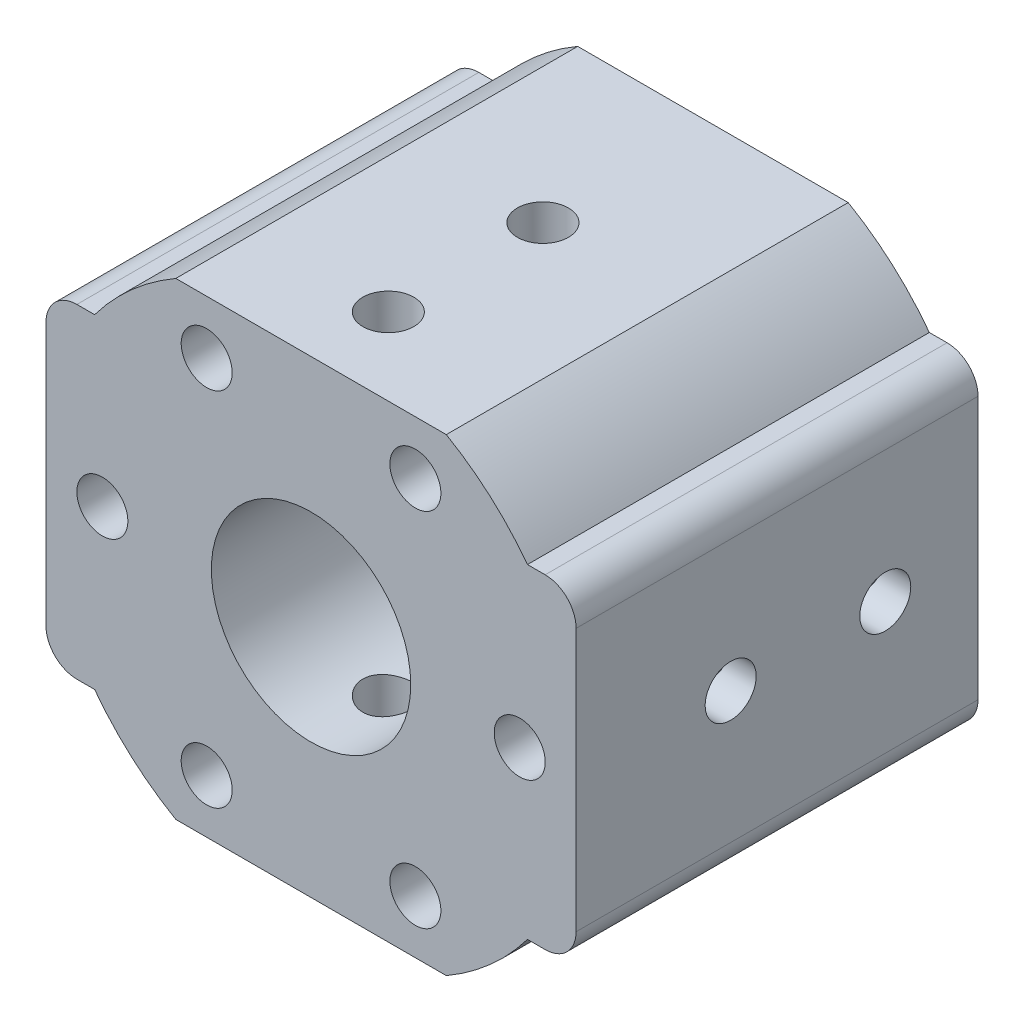
SolidWorks part; units mm, degrees
material "PLA"
ref_plane "前视基准面" through (0, 0, 0) normal (0, 0, 1) x (1, 0, 0)
ref_plane "上视基准面" through (0, 0, 0) normal (0, 1, 0) x (1, 0, 0)
ref_plane "右视基准面" through (0, 0, 0) normal (1, 0, 0) x (0, 0, -1)
other "Configuration Table"
sketch "草图1" plane through (0, 0, 0) normal (0, 0, 1) x (1, 0, 0)
  line L1 (17.5, 0) -> (8.75, 15.1554)
  line L2 (8.75, 15.1554) -> (-8.75, 15.1554)
  line L3 (-8.75, 15.1554) -> (-17.5, 0)
  line L4 (-17.5, 0) -> (-8.75, -15.1554)
  line L5 (-8.75, -15.1554) -> (8.75, -15.1554)
  line L6 (8.75, -15.1554) -> (17.5, 0)
  circle A1 centre (13.5, 0) radius 1.65 construction
  circle A2 centre (6.75, -11.6913) radius 1.65 construction
  circle A3 centre (-6.75, -11.6913) radius 1.65 construction
  circle A4 centre (-13.5, 0) radius 1.65 construction
  circle A5 centre (-6.75, 11.6913) radius 1.65 construction
  circle A6 centre (6.75, 11.6913) radius 1.65 construction
  arc A7 (-8.75, 15.1554) -> (-8.75, -15.1554) centre (0, 0) ccw
  arc A8 (8.75, -15.1554) -> (8.75, 15.1554) centre (0, 0) ccw
  point P17 (0, 0)
  dimension "D1" = 13.5
  dimension "D2" = 35
  dimension "D3" = 3.3
  dimension "D4" = 6
extrude "凸台-拉伸1" add sketch "草图1" along normal blind 30 contours L5 L6 L1 L2 L3 L4 A6 A5 A4 A3 A2 A1 | L3 A7 | L4 A7 | L1 A8 | L6 A8 region at (0, 0, 0) region at (13.942, -8.0494, 0) region at (13.942, 8.0494, 0) region at (-13.942, 8.0494, 0) region at (-13.942, -8.0494, 0)
sketch "草图3" plane through (0, 0, 30) normal (0, 0, 1) x (1, 0, 0)
  line L1 (-4.45, 4.45) -> (4.45, 4.45) construction
  line L2 (-4.45, 4.45) -> (-4.45, -4.45) construction
  line L3 (-4.45, -4.45) -> (4.45, -4.45) construction
  line L4 (4.45, 4.45) -> (4.45, -4.45) construction
  line L5 (-4.45, 4.45) -> (4.45, -4.45) construction
  line L6 (-4.45, -4.45) -> (4.45, 4.45) construction
  circle A0 centre (0, 0) radius 6.45
  point P0 (0, 0)
  dimension "D3" = 12.9
  dimension "D1" = 8.9
  dimension "D2" = 8.9
extrude "切除-拉伸1" cut sketch "草图3" against normal through all
sketch "草图4" plane through (0, 15.1554, 0) normal (0, 1, 0) x (1, 0, 0)
  line L0 (8.75, -30) -> (-8.75, -30) construction
  circle A0 centre (0, -15) radius 1.65
  circle A1 centre (0, -25) radius 1.65
  dimension "D1" = 5
  dimension "D2" = 10
  dimension "D3" = 3.3
extrude "切除-拉伸2" cut sketch "草图4" against normal through all
sketch "草图6" [suppressed] plane through (0, 0, 30) normal (0, 0, 1) x (1, 0, 0)
  circle A0 centre (-6.75, 11.6913) radius 3.25
  circle A1 centre (6.75, 11.6913) radius 3.25
  circle A2 centre (13.5, 0) radius 3.25
  circle A3 centre (6.75, -11.6913) radius 3.25
  circle A4 centre (-6.75, -11.6913) radius 3.25
  circle A5 centre (-13.5, 0) radius 3.25
  point P16 (0, 0)
  dimension "D1" = 6.5
  dimension "D2" = 6
extrude "切除-拉伸3" [suppressed] cut sketch "草图6" against normal blind 5
sketch "草图7" plane through (0, 0, 0) normal (1, 0, 0) x (0, 0, -1)
  line L0 (0, 0) -> (-25.3477, 0) construction
  line L1 (-30, 15.1554) -> (-30, -15.1554) construction
  line L2 (-30, 3.5) -> (0, 3.5)
  line L3 (-30, 3.5) -> (-30, 10.5)
  line L4 (-30, 10.5) -> (0, 10.5)
  line L5 (0, 3.5) -> (0, 10.5)
  line L6 (0, -15.1554) -> (0, 15.1554) construction
  line L7 (0, -3.5) -> (0, -10.5)
  line L8 (-30, -3.5) -> (0, -3.5)
  line L9 (-30, -3.5) -> (-30, -10.5)
  line L10 (-30, -10.5) -> (0, -10.5)
  dimension "D1" = 7
  dimension "D2" = 3.5
extrude "切除-拉伸4" cut sketch "草图7" against normal blind 30 from offset 14 offset against normal yes
extrude "切除-拉伸5" cut sketch "草图7<2>" along normal blind 30 from offset 14
sketch "草图7<2>" plane through (0, 0, 0) normal (1, 0, 0) x (0, 0, -1) same geometry as "草图7"
sketch "草图10" plane through (-14, 0, 0) normal (-1, 0, 0) x (0, 0, 1)
  line L0 (30, -3.5) -> (0, -3.5) construction
  line L1 (0, -3.5) -> (0, -10.5) construction
  line L2 (0, -10.5) -> (30, -10.5) construction
  line L3 (30, -10.5) -> (30, -3.5) construction
  line L4 (30, 3.5) -> (30, 10.5) construction
  line L5 (30, 10.5) -> (0, 10.5) construction
  line L6 (0, 10.5) -> (0, 3.5) construction
  line L7 (0, 3.5) -> (30, 3.5) construction
  line L8 (30, -3.5) -> (0, -3.5)
  line L9 (0, -3.5) -> (0, -10.5)
  line L10 (0, -10.5) -> (30, -10.5)
  line L11 (30, -10.5) -> (30, -3.5)
  line L12 (30, 3.5) -> (30, 10.5)
  line L13 (30, 10.5) -> (0, 10.5)
  line L14 (0, 10.5) -> (0, 3.5)
  line L15 (0, 3.5) -> (30, 3.5)
extrude "凸台-拉伸2" add sketch "草图10" along normal up to vertex (3.1464 mm away) up to point (-17.1464, 3.5, 30)
sketch "草图11" plane through (14, 0, 0) normal (1, 0, 0) x (0, 0, -1)
  line L0 (0, -3.5) -> (-30, -3.5) construction
  line L1 (-30, -3.5) -> (-30, -10.5) construction
  line L2 (-30, -10.5) -> (0, -10.5) construction
  line L3 (0, -10.5) -> (0, -3.5) construction
  line L4 (-30, 10.5) -> (-30, 3.5) construction
  line L5 (-30, 3.5) -> (0, 3.5) construction
  line L6 (0, 3.5) -> (0, 10.5) construction
  line L7 (0, 10.5) -> (-30, 10.5) construction
  line L8 (0, -3.5) -> (-30, -3.5)
  line L9 (-30, -3.5) -> (-30, -10.5)
  line L10 (-30, -10.5) -> (0, -10.5)
  line L11 (0, -10.5) -> (0, -3.5)
  line L12 (-30, 10.5) -> (-30, 3.5)
  line L13 (-30, 3.5) -> (0, 3.5)
  line L14 (0, 3.5) -> (0, 10.5)
  line L15 (0, 10.5) -> (-30, 10.5)
extrude "凸台-拉伸3" add sketch "草图11" along normal up to vertex (3.1464 mm away) up to point (17.1464, 3.5, 30)
sketch "草图12" plane through (-17.1464, 0, 0) normal (-1, 0, 0) x (0, 0, 1)
  line L0 (20, 15.1554) -> (20, -15.1554) construction
  line L1 (16.65, 15.1554) -> (13.35, 15.1554) construction
  line L2 (26.65, 15.1554) -> (23.35, 15.1554) construction
  line L3 (16.65, 15.1554) -> (13.35, 15.1554) construction
  line L4 (26.65, 15.1554) -> (23.35, 15.1554) construction
  line L7 (16.65, 15.1554) -> (23.35, 15.1554) construction
  circle A2 centre (20, 0) radius 1.65
  dimension "D1" = 3.3
extrude "切除-拉伸6" cut sketch "草图12" against normal through all
sketch "草图14" plane through (0, -15.1554, 0) normal (0, -1, 0) x (1, 0, 0)
  line L1 (-17.1464, 30) -> (-20.1283, 30)
  line L2 (-17.1464, 30) -> (-17.1464, -0.8267)
  line L3 (-17.1464, -0.8267) -> (-20.1283, -0.8267)
  line L4 (-20.1283, 30) -> (-20.1283, -0.8267)
  line L5 (17.1464, 30) -> (20.3756, 30)
  line L6 (17.1464, 30) -> (17.1464, -1.7911)
  line L7 (17.1464, -1.7911) -> (20.3756, -1.7911)
  line L8 (20.3756, 30) -> (20.3756, -1.7911)
extrude "切除-拉伸7" cut sketch "草图14" against normal through all
sketch "草图16" [suppressed] plane through (0, 0, 10) normal (0, 0, 1) x (1, 0, 0)
  circle A0 centre (0, 0) radius 6.8
  dimension "D1" = 13.6
extrude "切除-拉伸8" [suppressed] cut sketch "草图16" against normal through all
sketch "草图17" plane through (17.1464, 0, 0) normal (1, 0, 0) x (0, 0, -1)
  circle A0 centre (-10, 0) radius 1.65
  circle A1 centre (-20, 0) radius 1.65 construction
  dimension "D1" = 10
extrude "切除-拉伸9" cut sketch "草图17" against normal through all
sketch "草图18" plane through (0, 0, 0) normal (0, 0, -1) x (-1, 0, 0)
  line L6 (-14, 10.5) -> (-17.1464, 10.5)
  line L8 (17.1464, -10.5) -> (17.1464, 10.5)
  line L9 (17.1464, 10.5) -> (14, 10.5)
  line L10 (8.75, 15.1554) -> (-8.75, 15.1554)
  line L13 (-14, 10.5) -> (-17.1464, 10.5)
  line L14 (-8.75, -15.1554) -> (8.75, -15.1554)
  line L15 (14, -10.5) -> (17.1464, -10.5)
  line L16 (17.1464, -10.5) -> (17.1464, 10.5)
  line L17 (17.1464, 10.5) -> (14, 10.5)
  line L18 (8.75, 15.1554) -> (-8.75, 15.1554)
  line L22 (-8.75, -15.1554) -> (8.75, -15.1554)
  line L23 (14, -10.5) -> (17.1464, -10.5)
  line L24 (-17.1464, 10.5) -> (-17.1464, -10.5)
  line L25 (-17.1464, 10.5) -> (-17.1464, -10.5)
  line L26 (-17.1464, -10.5) -> (-14, -10.5)
  line L27 (-17.1464, -10.5) -> (-14, -10.5)
  arc A4 (14, 10.5) -> (8.75, 15.1554) centre (0, 0) ccw
  arc A5 (-8.75, 15.1554) -> (-14, 10.5) centre (0, 0) ccw
  arc A6 (-14, -10.5) -> (-8.75, -15.1554) centre (0, 0) ccw
  arc A7 (8.75, -15.1554) -> (14, -10.5) centre (0, 0) ccw
  arc A8 (14, 10.5) -> (8.75, 15.1554) centre (0, 0) ccw
  arc A9 (-8.75, 15.1554) -> (-14, 10.5) centre (0, 0) ccw
  arc A11 (8.75, -15.1554) -> (14, -10.5) centre (0, 0) ccw
  arc A13 (-14, -10.5) -> (-8.75, -15.1554) centre (0, 0) ccw
  dimension "D1" = 0
extrude "切除-拉伸10" cut sketch "草图18" against normal blind 5
sketch "草图19" plane through (0, 0, 30) normal (0, 0, 1) x (1, 0, 0)
  circle A0 centre (13.5, 0) radius 1.65
  circle A1 centre (6.75, -11.6913) radius 1.65
  circle A2 centre (-6.75, -11.6913) radius 1.65
  circle A3 centre (-13.5, 0) radius 1.65
  circle A4 centre (-6.75, 11.6913) radius 1.65
  circle A5 centre (6.75, 11.6913) radius 1.65
  point P16 (0, 0)
  dimension "D1" = 13.5
  dimension "D2" = 3.3
  dimension "D3" = 6
extrude "切除-拉伸11" cut sketch "草图19" against normal through all
fillet "圆角1" radius 2 4 edges at (17.1464, -10.5, 17.5) (17.1464, 10.5, 17.5) (-17.1464, -10.5, 17.5) (-17.1464, 10.5, 17.5)
ref_plane "基准面1" [suppressed] through (0, 0, 9) normal (0, 0, 1) x (1, 0, 0)
mirror "镜向2" [suppressed] about plane through (0, 0, 9) normal (0, 0, 1) of bodies 115
sketch "草图21" [suppressed] plane through (0, 15.1554, 0) normal (0, 1, 0) x (1, 0, 0)
  line L0 (17.1464, -9) -> (-40.6903, -9) construction
  line L1 (17.1464, 12) -> (17.1464, -30) construction
  circle A0 centre (0, -3) radius 1.65
  circle A1 centre (0, -15) radius 1.65
  circle A2 centre (0, -25) radius 1.65 construction
  dimension "D1" = 10
extrude "切除-拉伸12" [suppressed] cut sketch "草图21" against normal through all
sketch "草图22" [suppressed] plane through (0, 0, 18) normal (0, 0, 1) x (1, 0, 0)
  line L4 (-7.85, -7.85) -> (7.85, -7.85)
  line L5 (7.85, -7.85) -> (7.85, 7.85)
  line L6 (7.85, 7.85) -> (-7.85, 7.85)
  line L7 (-7.85, 7.85) -> (-7.85, -7.85)
  line L8 (-7.85, -7.85) -> (7.85, -7.85)
  line L9 (7.85, -7.85) -> (7.85, 7.85)
  line L10 (7.85, 7.85) -> (-7.85, 7.85)
  line L11 (-7.85, 7.85) -> (-7.85, -7.85)
  dimension "D1" = 0
extrude "切除-拉伸13" [suppressed] cut sketch "草图22" against normal through all
sketch "草图23" [suppressed] plane through (0, 0, -12) normal (0, 0, -1) x (-1, 0, 0)
  line L0 (7.85, -7.85) -> (-7.85, -7.85) construction
  line L1 (-6.35, 6.35) -> (6.35, 6.35)
  line L2 (-6.35, 6.35) -> (-6.35, -6.35)
  line L3 (-6.35, -6.35) -> (6.35, -6.35)
  line L4 (6.35, 6.35) -> (6.35, -6.35)
  line L5 (-6.35, 6.35) -> (6.35, -6.35) construction
  line L6 (-6.35, -6.35) -> (6.35, 6.35) construction
  line L7 (7.85, 7.85) -> (7.85, -7.85) construction
  line L8 (-7.85, 7.85) -> (7.85, 7.85) construction
  line L9 (-7.85, -7.85) -> (-7.85, 7.85) construction
  line L10 (7.85, -7.85) -> (-7.85, -7.85)
  line L11 (7.85, 7.85) -> (7.85, -7.85)
  line L12 (-7.85, 7.85) -> (7.85, 7.85)
  line L13 (-7.85, -7.85) -> (-7.85, 7.85)
  point P0 (0, 0)
  dimension "D1" = 12.7
  dimension "D2" = 12.7
extrude "凸台-拉伸5" [suppressed] add sketch "草图23" against normal blind 21
sketch "草图24" plane through (0, 0, 5) normal (0, 0, -1) x (-1, 0, 0)
  line L8 (-17.1464, 8.5) -> (-17.1464, -8.5)
  line L9 (-15.1464, -10.5) -> (-14, -10.5)
  line L10 (-8.75, -15.1554) -> (8.75, -15.1554)
  line L11 (14, -10.5) -> (15.1464, -10.5)
  line L12 (17.1464, -8.5) -> (17.1464, 8.5)
  line L13 (15.1464, 10.5) -> (14, 10.5)
  line L14 (8.75, 15.1554) -> (-8.75, 15.1554)
  line L15 (-14, 10.5) -> (-15.1464, 10.5)
  line L16 (-17.1464, 8.5) -> (-17.1464, -8.5)
  line L17 (-15.1464, -10.5) -> (-14, -10.5)
  line L18 (-8.75, -15.1554) -> (8.75, -15.1554)
  line L19 (14, -10.5) -> (15.1464, -10.5)
  line L20 (17.1464, -8.5) -> (17.1464, 8.5)
  line L21 (15.1464, 10.5) -> (14, 10.5)
  line L22 (8.75, 15.1554) -> (-8.75, 15.1554)
  line L23 (-14, 10.5) -> (-15.1464, 10.5)
  arc A8 (-17.1464, -8.5) -> (-15.1464, -10.5) centre (-15.1464, -8.5) ccw
  arc A9 (-14, -10.5) -> (-8.75, -15.1554) centre (0, 0) ccw
  arc A10 (8.75, -15.1554) -> (14, -10.5) centre (0, 0) ccw
  arc A11 (15.1464, -10.5) -> (17.1464, -8.5) centre (15.1464, -8.5) ccw
  arc A12 (17.1464, 8.5) -> (15.1464, 10.5) centre (15.1464, 8.5) ccw
  arc A13 (14, 10.5) -> (8.75, 15.1554) centre (0, 0) ccw
  arc A14 (-8.75, 15.1554) -> (-14, 10.5) centre (0, 0) ccw
  arc A15 (-15.1464, 10.5) -> (-17.1464, 8.5) centre (-15.1464, 8.5) ccw
  arc A16 (-17.1464, -8.5) -> (-15.1464, -10.5) centre (-15.1464, -8.5) ccw
  arc A17 (-14, -10.5) -> (-8.75, -15.1554) centre (0, 0) ccw
  arc A18 (8.75, -15.1554) -> (14, -10.5) centre (0, 0) ccw
  arc A19 (15.1464, -10.5) -> (17.1464, -8.5) centre (15.1464, -8.5) ccw
  arc A20 (17.1464, 8.5) -> (15.1464, 10.5) centre (15.1464, 8.5) ccw
  arc A21 (14, 10.5) -> (8.75, 15.1554) centre (0, 0) ccw
  arc A22 (-8.75, 15.1554) -> (-14, 10.5) centre (0, 0) ccw
  arc A23 (-15.1464, 10.5) -> (-17.1464, 8.5) centre (-15.1464, 8.5) ccw
  dimension "D1" = 0
extrude "凸台-拉伸6" add sketch "草图24" along normal blind 1
